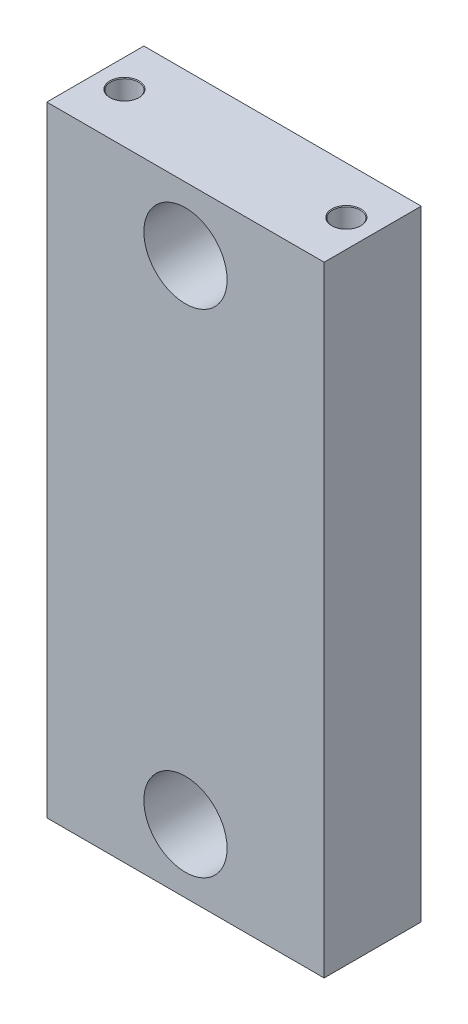
SolidWorks part; units mm, degrees
ref_plane "Front Plane" through (0, 0, 0) normal (0, 0, 1) x (1, 0, 0)
ref_plane "Top Plane" through (0, 0, 0) normal (0, 1, 0) x (1, 0, 0)
ref_plane "Right Plane" through (0, 0, 0) normal (1, 0, 0) x (0, 0, -1)
sketch "Sketch2" plane through (0, 0, 0) normal (0, 0, 1) x (1, 0, 0)
  line L8 (-5, -27.35) -> (5, -27.35)
  line L9 (-5, -27.35) -> (-5, -5)
  line L10 (-5, -5) -> (5, -5)
  line L11 (5, -27.35) -> (5, -5)
  line L12 (-5, -27.35) -> (5, -5) construction
  line L13 (-5, -5) -> (5, -27.35) construction
  circle A9 centre (0, -7.3) radius 1.5
  circle A10 centre (0, -25.05) radius 1.5
  point P0 (0, 0)
  point P8 (0, -16.175)
  dimension "D2" = 5
  dimension "D4" = 3
  dimension "D11" = 3
  dimension "D12" = 17.75
  dimension "D6" = 22.35
  dimension "D7" = 10
extrude "Boss-Extrude1" add sketch "Sketch2" along normal blind 3.5 contours L8 L11 L9 region at (0, -16.175, 0)
sketch3d "3DSketch2" plane through (0, 0, 0) normal (0, 0, 1) x (1, 0, 0)
sketch "Sketch8" plane through (0, -5, 0) normal (0, 1, 0) x (1, 0, 0)
  line L0 (-4, -1.7) -> (4, -1.7) construction
  line L1 (-4, -0.9) -> (4, -0.9)
  line L2 (-4, -2.5) -> (4, -2.5)
  line L3 (-5, -3.5) -> (-5, 0) construction
  line L5 (-5, 0) -> (5, 0) construction
  arc A0 (-4, -0.9) -> (-4, -2.5) centre (-4, -1.7) ccw
  arc A1 (4, -2.5) -> (4, -0.9) centre (4, -1.7) ccw
  point P2 (0, -1.7)
  dimension "D1" = 8
  dimension "D2" = 1
  dimension "D3" = 0.8
  dimension "D4" = 0.9
hole_wizard "Ø1.0mm Dowel Hole1" positions "3DSketch5" profile "Sketch9" hole size "Ø1.0" standard "ANSI Metric"
sketch3d "3DSketch5"
  point P0 (-4, -5, 1.7)
  point P3 (4, -5, 1.7)
sketch "Sketch9" plane through (-4, -5, 1.7) normal (1, 0, 0) x (0, 0, 1)
  line L0 (0, 0) -> (0, 3.3004)
  line L1 (0, 3.3004) -> (0.5, 3)
  line L2 (0.5, 3) -> (0.5, 0.025)
  line L3 (0.5, 0.025) -> (0.525, 0)
  line L5 (0.525, 0) -> (0, 0)
  line L6 (-0.5, 0.025) -> (-0.525, 0) construction
  line L10 (0, 3.3004) -> (-0.5, 3) construction
  line L11 (0, -6.35) -> (0, 107.95) construction
  dimension "Hole Dia." = 1
  dimension "Hole Depth" = 3
  dimension "Near C'Sink Dia." = 1.05
  dimension "Near C'Sink Angle" = 90
  dimension "Drill Angle" = 118
